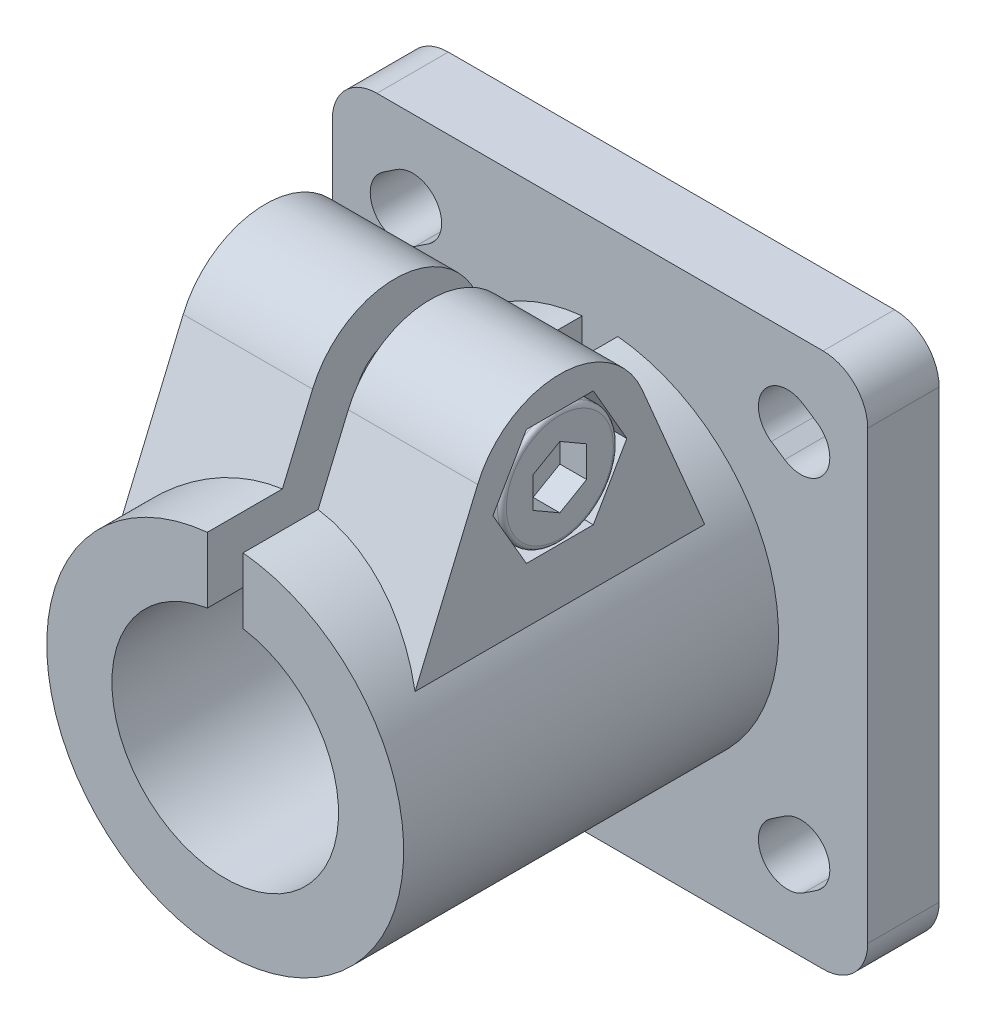
SolidWorks part; units mm, degrees
ref_plane "Front Plane" through (0, 0, 0) normal (0, 0, 1) x (1, 0, 0)
ref_plane "Top Plane" through (0, 0, 0) normal (0, 1, 0) x (1, 0, 0)
ref_plane "Right Plane" through (0, 0, 0) normal (1, 0, 0) x (0, 0, -1)
sketch "Sketch1" plane through (0, 0, 0) normal (0, 0, 1) x (1, 0, 0)
  line L1 (-16.5, 0) -> (16.5, 0) construction
  line L3 (-21, 21) -> (21, -21) construction
  line L5 (-22.5, 20) -> (22.5, 20) construction
  line L7 (-22.5, 20) -> (-22.5, -20) construction
  line L8 (-22.5, -20) -> (22.5, -20) construction
  line L9 (22.5, 20) -> (22.5, -20) construction
  line L10 (-21, 21) -> (21, 21) construction
  line L11 (-21, 21) -> (-21, -21) construction
  line L12 (-21, -21) -> (21, -21) construction
  line L13 (21, 21) -> (21, -21) construction
  line L14 (22.5, 20) -> (-22.5, -20) construction
  line L15 (30, 30) -> (-30, -30) construction
  line L16 (-30, 30) -> (30, 30) construction
  line L17 (-30, 30) -> (-30, -30) construction
  line L18 (-30, -30) -> (30, -30) construction
  line L19 (30, 30) -> (30, -30) construction
  line L20 (-22.5, -20) -> (-21, -21) construction
  line L21 (-20.6972, -17.2958) -> (-19.1972, -18.2958)
  line L22 (-24.3028, -22.7042) -> (-22.8028, -23.7042)
  line L23 (21, -21) -> (22.5, -20) construction
  line L24 (19.1972, -18.2958) -> (20.6972, -17.2958)
  line L25 (22.8028, -23.7042) -> (24.3028, -22.7042)
  line L26 (22.5, 20) -> (21, 21) construction
  line L27 (20.6972, 17.2958) -> (19.1972, 18.2958)
  line L28 (24.3028, 22.7042) -> (22.8028, 23.7042)
  line L29 (-21, 21) -> (-22.5, 20) construction
  line L30 (-19.1972, 18.2958) -> (-20.6972, 17.2958)
  line L31 (-22.8028, 23.7042) -> (-24.3028, 22.7042)
  circle A0 centre (0, 0) radius 12.7 construction
  arc A1 (-20.6972, -17.2958) -> (-24.3028, -22.7042) centre (-22.5, -20) ccw
  arc A4 (-22.8028, -23.7042) -> (-19.1972, -18.2958) centre (-21, -21) ccw
  arc A5 (19.1972, -18.2958) -> (22.8028, -23.7042) centre (21, -21) ccw
  arc A6 (24.3028, -22.7042) -> (20.6972, -17.2958) centre (22.5, -20) ccw
  arc A7 (20.6972, 17.2958) -> (24.3028, 22.7042) centre (22.5, 20) ccw
  arc A8 (22.8028, 23.7042) -> (19.1972, 18.2958) centre (21, 21) ccw
  arc A9 (-19.1972, 18.2958) -> (-22.8028, 23.7042) centre (-21, 21) ccw
  arc A10 (-24.3028, 22.7042) -> (-20.6972, 17.2958) centre (-22.5, 20) ccw
  point P15 (0, 12.7)
  point P18 (-21.75, -20.5)
  point P34 (0, -12.7)
  point P41 (21.75, -20.5)
  point P46 (21.75, 20.5)
  point P51 (-21.75, 20.5)
sketch "Sketch2" plane through (0, 0, 0) normal (1, 0, 0) x (0, 0, -1)
  line L0 (0, 0) -> (-50, 0) construction
  line L2 (-50, 20) -> (-50, -20) construction
  line L3 (0, 30) -> (0, -30) construction
  line L4 (-8, 30) -> (-8, -30) construction
  line L5 (-29, 20) -> (-50, 20) construction
  circle A0 centre (-29, 24) radius 4 construction
  point P6 (-8, 0)
  dimension "S" = 8
  dimension "D" = 40
  dimension "L" = 50
  dimension "N" = 8
  dimension "R" = 29
sketch "Sketch3" plane through (0, 0, 0) normal (0, 0, 1) x (1, 0, 0)
  line L0 (-30, 30) -> (-30, -30) construction
  line L1 (-30, 30) -> (30, 30) construction
  line L2 (30, 30) -> (30, -30) construction
  line L3 (-30, -30) -> (30, -30) construction
  line L4 (-30, 25) -> (-30, -25)
  line L5 (-25, 30) -> (25, 30)
  line L6 (30, 25) -> (30, -25)
  line L7 (-25, -30) -> (25, -30)
  arc A0 (-25, 30) -> (-30, 25) centre (-25, 25) ccw
  arc A1 (25, 30) -> (30, 25) centre (25, 25) cw
  arc A2 (30, -25) -> (25, -30) centre (25, -25) cw
  arc A3 (-30, -25) -> (-25, -30) centre (-25, -25) ccw
  dimension "D1" = 5
extrude "Boss-Extrude1" add sketch "Sketch3" along normal up to vertex (8 mm away) up to point (0, 0, 8)
sketch "Sketch4" plane through (0, 0, 8) normal (0, 0, 1) x (1, 0, 0)
  circle A0 centre (0, 0) radius 20
extrude "Boss-Extrude2" add sketch "Sketch4" along normal up to vertex (42 mm away) up to point (0, 0, 50)
sketch "Sketch5" plane through (0, 0, 0) normal (1, 0, 0) x (0, 0, -1)
  line L0 (-50, 0) -> (-38.2111, 27.893)
  line L1 (-50, 0) -> (-8, 0)
  line L2 (-8, 0) -> (-19.7889, 27.893)
  line L3 (-29, 0) -> (-29, 34) construction
  arc A0 (-19.7889, 27.893) -> (-38.2111, 27.893) centre (-29, 24) ccw
  dimension "R" = 10
extrude "Boss-Extrude3" add sketch "Sketch5" along normal mid plane 33
sketch "Sketch6" plane through (0, 0, 0) normal (0, 0, 1) x (1, 0, 0)
  line L0 (-19.1972, 18.2958) -> (-20.6972, 17.2958) construction
  line L1 (-19.1972, 18.2958) -> (-20.6972, 17.2958)
  line L2 (-22.8028, 23.7042) -> (-24.3028, 22.7042) construction
  line L3 (24.3028, 22.7042) -> (22.8028, 23.7042) construction
  line L4 (20.6972, 17.2958) -> (19.1972, 18.2958) construction
  line L5 (22.8028, -23.7042) -> (24.3028, -22.7042) construction
  line L6 (19.1972, -18.2958) -> (20.6972, -17.2958) construction
  line L7 (-24.3028, -22.7042) -> (-22.8028, -23.7042) construction
  line L8 (-20.6972, -17.2958) -> (-19.1972, -18.2958) construction
  line L9 (-22.8028, 23.7042) -> (-24.3028, 22.7042)
  line L10 (24.3028, 22.7042) -> (22.8028, 23.7042)
  line L11 (20.6972, 17.2958) -> (19.1972, 18.2958)
  line L12 (22.8028, -23.7042) -> (24.3028, -22.7042)
  line L13 (19.1972, -18.2958) -> (20.6972, -17.2958)
  line L14 (-24.3028, -22.7042) -> (-22.8028, -23.7042)
  line L15 (-20.6972, -17.2958) -> (-19.1972, -18.2958)
  arc A0 (-24.3028, 22.7042) -> (-20.6972, 17.2958) centre (-22.5, 20) ccw construction
  arc A1 (-19.1972, 18.2958) -> (-22.8028, 23.7042) centre (-21, 21) ccw construction
  arc A2 (20.6972, 17.2958) -> (24.3028, 22.7042) centre (22.5, 20) ccw construction
  arc A3 (22.8028, 23.7042) -> (19.1972, 18.2958) centre (21, 21) ccw construction
  arc A4 (19.1972, -18.2958) -> (22.8028, -23.7042) centre (21, -21) ccw construction
  arc A5 (24.3028, -22.7042) -> (20.6972, -17.2958) centre (22.5, -20) ccw construction
  arc A6 (-22.8028, -23.7042) -> (-19.1972, -18.2958) centre (-21, -21) ccw construction
  arc A7 (-20.6972, -17.2958) -> (-24.3028, -22.7042) centre (-22.5, -20) ccw construction
  arc A8 (-24.3028, 22.7042) -> (-20.6972, 17.2958) centre (-22.5, 20) ccw
  arc A9 (-19.1972, 18.2958) -> (-22.8028, 23.7042) centre (-21, 21) ccw
  arc A10 (20.6972, 17.2958) -> (24.3028, 22.7042) centre (22.5, 20) ccw
  arc A11 (22.8028, 23.7042) -> (19.1972, 18.2958) centre (21, 21) ccw
  arc A12 (19.1972, -18.2958) -> (22.8028, -23.7042) centre (21, -21) ccw
  arc A13 (24.3028, -22.7042) -> (20.6972, -17.2958) centre (22.5, -20) ccw
  arc A14 (-22.8028, -23.7042) -> (-19.1972, -18.2958) centre (-21, -21) ccw
  arc A15 (-20.6972, -17.2958) -> (-24.3028, -22.7042) centre (-22.5, -20) ccw
  circle A16 centre (0, 0) radius 12.7 construction
  circle A17 centre (0, 0) radius 12.7
extrude "Cut-Extrude1" cut sketch "Sketch6" along normal up to next
sketch "Sketch7" plane through (0, 0, 50) normal (0, 0, 1) x (1, 0, 0)
  line L1 (-2, 34) -> (2, 34)
  line L2 (-2, 34) -> (-2, 12.5415)
  line L4 (2, 34) -> (2, 12.5415)
  circle A0 centre (0, 0) radius 12.7 construction
  arc A1 (2, 12.5415) -> (-2, 12.5415) centre (0, 0) ccw
  dimension "D1" = 4
extrude "Cut-Extrude2" cut sketch "Sketch7" against normal up to vertex (42 mm away) up to point (0, 0, 8)
sketch "Sketch8" plane through (0, 0, 0) normal (1, 0, 0) x (0, 0, -1)
  circle A5 centre (-29, 24) radius 4.5
  circle A6 centre (-29, 24) radius 4.5
  dimension "D1" = 0.5
extrude "Cut-Extrude3" cut sketch "Sketch8" against normal up to next and the other way up to next
sketch "Sketch9" plane through (16.5, 0, 0) normal (1, 0, 0) x (0, 0, -1)
  line L1 (-32.7528, 30.5) -> (-36.5056, 24)
  line L2 (-36.5056, 24) -> (-32.7528, 17.5)
  line L3 (-32.7528, 17.5) -> (-25.2472, 17.5)
  line L4 (-25.2472, 17.5) -> (-21.4944, 24)
  line L5 (-21.4944, 24) -> (-25.2472, 30.5)
  line L6 (-25.2472, 30.5) -> (-32.7528, 30.5)
  circle A0 centre (-29, 24) radius 6.5 construction
  dimension "Hex" = 13
extrude "Cut-Extrude4" cut sketch "Sketch9" against normal blind 8
mirror "Mirror1" about plane through (0, 0, 0) normal (1, 0, 0) of "Cut-Extrude4"
sketch "Sketch10" plane through (8.5, 0, 0) normal (1, 0, 0) x (0, 0, -1)
  circle A0 centre (-29, 24) radius 4 construction
  circle A1 centre (-29, 24) radius 4
extrude "Boss-Extrude4" add sketch "Sketch10" against normal blind 25 separate body
sketch "Sketch11" plane through (-16.5, 0, 0) normal (-1, 0, 0) x (0, 0, 1)
  circle A1 centre (29, 24) radius 4
  circle A2 centre (29, 24) radius 4
  point P0 (29, 28)
  dimension "D1" = 0
curve "Helix/Spiral1" pitch 1.25 height 26.25 turns 21 parameters "Pitch"=1.25
chamfer "Chamfer1" distance 0.767 angle 45 1 edges at (-16.5, 24, 25)
ref_plane "Plane1" through (0, 0, 29) normal (0, 0, 1) x (1, 0, 0)
sketch "Sketch12" plane through (0, 0, 29) normal (0, 0, 1) x (1, 0, 0)
  line L0 (-17.6719, 28.1353) -> (-16.4219, 28.1353) construction
  line L1 (-16.4219, 28.1353) -> (-17.0469, 27.0528) construction
  line L2 (-17.0469, 27.0528) -> (-17.6719, 28.1353) construction
  line L3 (-17.125, 27.1881) -> (-16.9688, 27.1881) construction
  line L4 (-16.5, 28) -> (-17.5938, 28) construction
  line L5 (-17.0469, 27.0528) -> (-17.0469, 27.1881) construction
  line L6 (-17.0469, 28) -> (-17.0469, 28.1353) construction
  line L7 (-17.6328, 28.0677) -> (-17.125, 27.1881)
  line L8 (-17.125, 27.1881) -> (-16.9688, 27.1881)
  line L9 (-16.9688, 27.1881) -> (-16.4609, 28.0677)
  line L10 (-16.4609, 28.0677) -> (-17.6328, 28.0677)
  point P13 (-17.0469, 28.0677)
  dimension "D1" = 1.25
  dimension "D2" = 0.1562
sweep "Cut-Sweep1" cut profiles "Sketch12" path "Helix/Spiral1"
sketch "Sketch13" plane through (8.5, 0, 0) normal (1, 0, 0) x (0, 0, -1)
  circle A0 centre (-29, 24) radius 6.5
  dimension "Screw Head OD" = 13
extrude "Boss-Extrude5" add sketch "Sketch13" along normal blind 8
sketch "Sketch14" plane through (16.5, 0, 0) normal (1, 0, 0) x (0, 0, -1)
  line L1 (-29, 27.4641) -> (-32, 25.7321)
  line L2 (-32, 25.7321) -> (-32, 22.2679)
  line L3 (-32, 22.2679) -> (-29, 20.5359)
  line L4 (-29, 20.5359) -> (-26, 22.2679)
  line L5 (-26, 22.2679) -> (-26, 25.7321)
  line L6 (-26, 25.7321) -> (-29, 27.4641)
  circle A0 centre (-29, 24) radius 3 construction
  dimension "Screw Hex" = 6
extrude "Cut-Extrude5" cut sketch "Sketch14" against normal blind 3
fillet "Fillet1" radius 0.5 2 edges at (8.5, 24, 22.5) (16.5, 24, 22.5)
sketch "Sketch15" plane through (-8.5, 0, 0) normal (-1, 0, 0) x (0, 0, 1)
  line L1 (36.5056, 24) -> (32.7528, 30.5)
  line L2 (32.7528, 30.5) -> (25.2472, 30.5)
  line L3 (25.2472, 30.5) -> (21.4944, 24)
  line L4 (21.4944, 24) -> (25.2472, 17.5)
  line L5 (25.2472, 17.5) -> (32.7528, 17.5)
  line L6 (32.7528, 17.5) -> (36.5056, 24)
  circle A0 centre (29, 24) radius 6.5 construction
  circle A1 centre (29, 24) radius 3.3235
  circle A2 centre (29, 24) radius 7.5056 construction
  point P11 (29, 31.5056)
  dimension "Nut Hex" = 13
  dimension "Nut ID" = 6.647
extrude "Boss-Extrude6" add sketch "Sketch15" along normal blind 8 separate body
sketch "Sketch16" plane through (0, 0, 29) normal (0, 0, 1) x (1, 0, 0)
  line L0 (-8.5, 31.5056) -> (-8.5, 30.5)
  line L1 (-8.5, 30.5) -> (-8.7694, 31.5056)
  line L2 (-8.7694, 31.5056) -> (-8.5, 31.5056)
  line L3 (-13.7306, 31.5056) -> (-14, 31.5056)
  line L4 (-14, 31.5056) -> (-16.5, 31.5056)
  line L5 (-16.5, 31.5056) -> (-16.5, 28.8964)
  line L6 (-13.7306, 31.5056) -> (-14, 30.5)
  line L7 (-16.5, 30.5) -> (-8.5, 30.5) construction
  line L10 (-14, 30.5) -> (-16.2307, 29.34)
  line L11 (-8.5, 24) -> (-16.5, 24) construction
  line L12 (-16.5, 27.3235) -> (-16.5, 20.6765) construction
  line L13 (-14, 31.5056) -> (-14, 30.5) construction
  line L14 (-16.5, 24) -> (-16.5, 30.5) construction
  arc A0 (-16.2307, 29.34) -> (-16.5, 28.8964) centre (-16, 28.8964) ccw
  point P8 (-16.5, 29.2)
  dimension "R" = 0.5
  dimension "D1" = 5.5
  dimension "A" = 15
  dimension "D2" = 10.4
revolve "Cut-Revolve1" cut sketch "Sketch16" angle 360 about L11
chamfer "Chamfer2" distance 0.4 angle 45 2 edges at (-8.5, 24, 32.3235) (-16.5, 24, 32.3235)
equation "\"D3@Helix/Spiral1\" = \"Pitch@Helix/Spiral1\" + \"Screw Length@Boss-Extrude4\""
equation "\"D1@Boss-Extrude3\" = \"P@Sketch1\""
equation "\"D1@Sketch12\" = \"Pitch@Helix/Spiral1\""
equation "\"D2@Sketch12\" = \"D1@Sketch12\" / 8"
